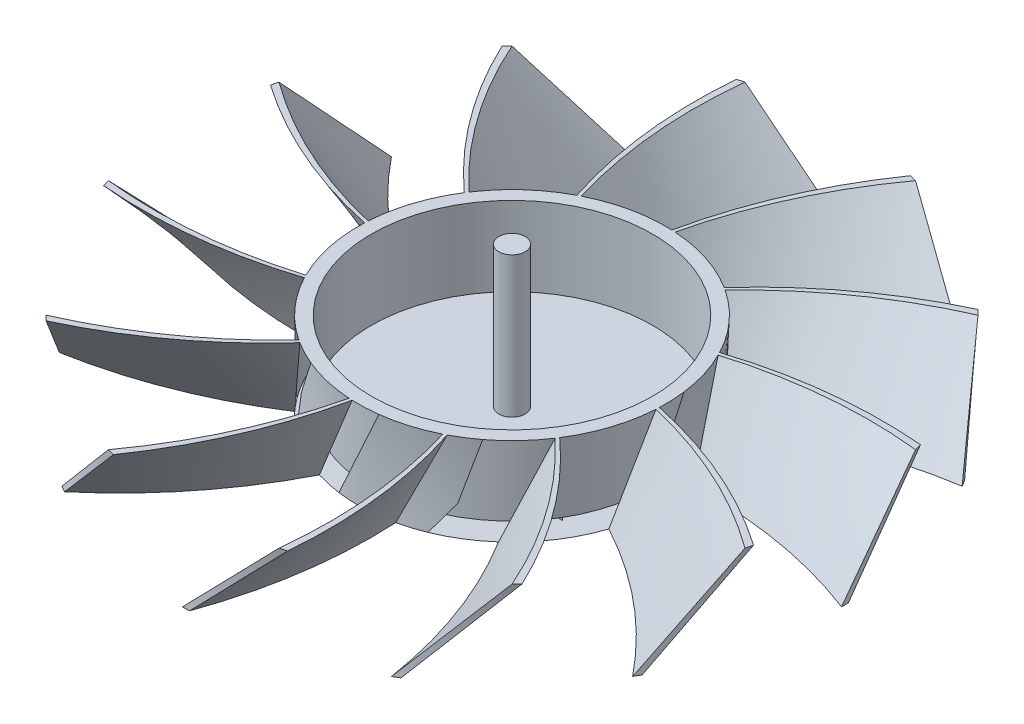
SolidWorks part; units mm, degrees
ref_plane "Front Plane" through (0, 0, 0) normal (0, 0, 1) x (1, 0, 0)
ref_plane "Top Plane" through (0, 0, 0) normal (0, 1, 0) x (1, 0, 0)
ref_plane "Right Plane" through (0, 0, 0) normal (1, 0, 0) x (0, 0, -1)
sketch "Sketch1" plane through (0, 0, 0) normal (0, 1, 0) x (1, 0, 0)
  line L0 (0, -45.273) -> (0, 73.6579) construction
  arc A0 (-3.8386, 17.0738) -> (-3.4735, 17.1518) centre (0, 0) ccw
  arc A2 (-3.4735, 17.1518) -> (0, 37.5) centre (48.5019, 18.75) cw
  arc A3 (-3.8386, 17.0738) -> (-0.8, 37.4915) centre (48.0909, 19.7804) cw
  arc A4 (0, 37.5) -> (-0.8, 37.4915) centre (0, 0) ccw
  dimension "D1" = 75
  dimension "D2" = 35
  dimension "D3" = 0.8
  dimension "D4" = 52
  dimension "D5" = 52
ref_plane "Plane1" through (0, 10, 0) normal (0, 1, 0) x (1, 0, 0)
sketch "Sketch2" plane through (0, 10, 0) normal (0, 1, 0) x (1, 0, 0)
  line L0 (-41.0978, 153.3791) -> (0, 0) construction
  line L1 (0, -45.273) -> (0, 73.6579) construction
  arc A0 (-8.1268, 15.4985) -> (-7.7944, 15.6684) centre (0, 0) ccw
  arc A1 (-9.7057, 36.2222) -> (-10.4762, 36.0069) centre (0, 0) ccw
  arc A2 (-7.7944, 15.6684) -> (-9.7057, 36.2222) centre (41.9964, 30.6643) cw
  arc A3 (-8.1268, 15.4985) -> (-10.4762, 36.0069) centre (41.3327, 31.5532) cw
  dimension "D1" = 0.8
  dimension "D2" = 52
  dimension "D3" = 52
  dimension "D4" = 15
loft "Loft2" add profiles "Sketch2", "Sketch1" connector at (-9.7057, 10, -36.2222) connector at (0, 0, -37.5)
pattern_circular "CirPattern1" count 12 over 360 about axis through (0, 10, 0) along (0, 1, 0) of "Loft2"
sketch "Sketch3" plane through (0, 0, 0) normal (0, -1, 0) x (1, 0, 0)
  line L0 (-14.0963, -1.9929) -> (12.6381, -1.9929) construction
  text T0 "SABRE" font "@Adobe Heiti Std R" height in points 18
extrude "Cut-Extrude1" cut sketch "Sketch3" against normal blind 0.5
sketch "Sketch4" plane through (0, 0, 0) normal (0, -1, 0) x (1, 0, 0)
  line L0 (-13.0898, 7.3705) -> (-1.5898, 7.3705)
  line L1 (-1.5898, 7.3705) -> (-1.5898, 3.5942)
  line L2 (-1.5898, 3.5942) -> (-3.5898, 3.5942)
  line L3 (-3.5898, 3.5942) -> (-3.5898, 5.3705)
  line L4 (-3.5898, 5.3705) -> (-11.0898, 5.3705)
  line L5 (-11.0898, 5.3705) -> (-13.0898, 7.3705)
  line L6 (0, -5.8284) -> (0, 10.7386) construction
  line L7 (-3.5898, -2.7969) -> (-3.5898, -12.2467)
  line L8 (-3.5898, -12.2467) -> (-1.5898, -14.2467)
  line L9 (-1.5898, -14.2467) -> (-1.5898, -2.7969)
  line L10 (-1.5898, -2.7969) -> (-3.5898, -2.7969)
  line L11 (3.5898, -2.7969) -> (3.5898, -12.2467)
  line L12 (3.5898, -12.2467) -> (1.5898, -14.2467)
  line L13 (1.5898, -14.2467) -> (1.5898, -2.7969)
  line L14 (1.5898, -2.7969) -> (3.5898, -2.7969)
  line L15 (3.5898, 3.5942) -> (3.5898, 5.3705)
  line L16 (1.5898, 7.3705) -> (1.5898, 3.5942)
  line L17 (1.5898, 3.5942) -> (3.5898, 3.5942)
  line L18 (11.0898, 5.3705) -> (13.0898, 7.3705)
  line L19 (3.5898, 5.3705) -> (11.0898, 5.3705)
  line L20 (13.0898, 7.3705) -> (1.5898, 7.3705)
  dimension "D1" = 45
  dimension "D2" = 2
  dimension "D3" = 2
  dimension "D4" = 11.5
extrude "Cut-Extrude2" cut sketch "Sketch4" against normal blind 0.5
sketch "Sketch5" plane through (0, 10, 0) normal (0, 1, 0) x (1, 0, 0)
  circle A0 centre (0, 0) radius 16
  dimension "D1" = 32
extrude "Cut-Extrude3" cut sketch "Sketch5" against normal blind 9
sketch "Sketch6" plane through (0, 1, 0) normal (0, 1, 0) x (1, 0, 0)
  circle A0 centre (0, 0) radius 1.5
  dimension "D1" = 3
extrude "Boss-Extrude1" add sketch "Sketch6" along normal blind 16
